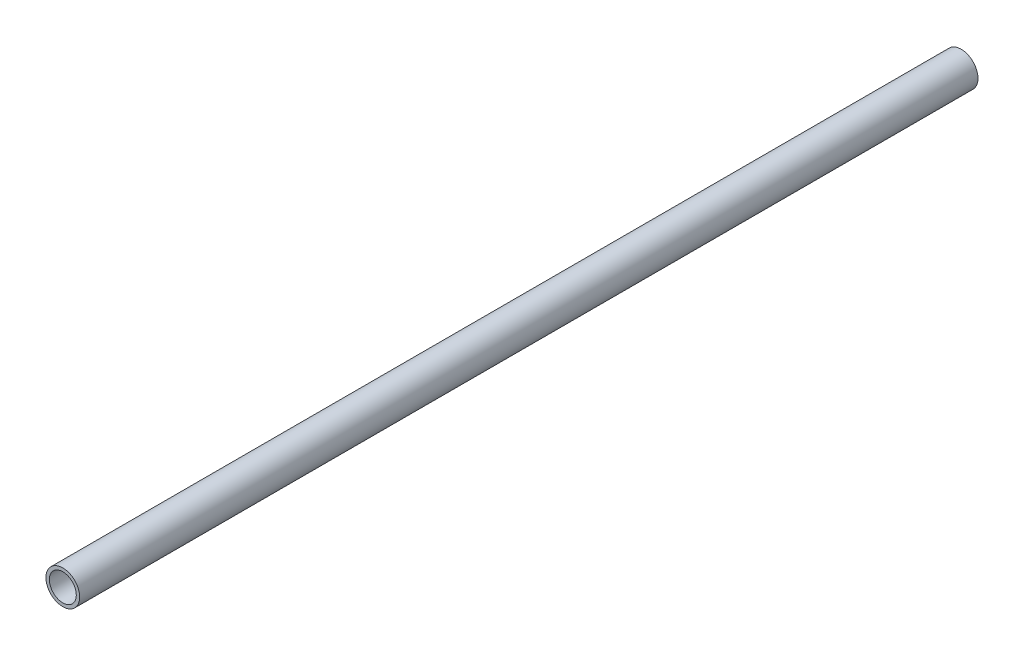
SolidWorks part; units mm, degrees
material "6061 Alloy"
ref_plane "Front Plane" through (0, 0, 0) normal (0, 0, 1) x (1, 0, 0)
ref_plane "Top Plane" through (0, 0, 0) normal (0, 1, 0) x (1, 0, 0)
ref_plane "Right Plane" through (0, 0, 0) normal (1, 0, 0) x (0, 0, -1)
sketch "Sketch1" plane through (0, 0, 0) normal (0, 0, 1) x (1, 0, 0)
  circle A0 centre (390.7614, 31.0815) radius 7.5
  circle A1 centre (390.7614, 31.0815) radius 6
extrude "Boss-Extrude1" add sketch "Sketch1" along normal blind 400
